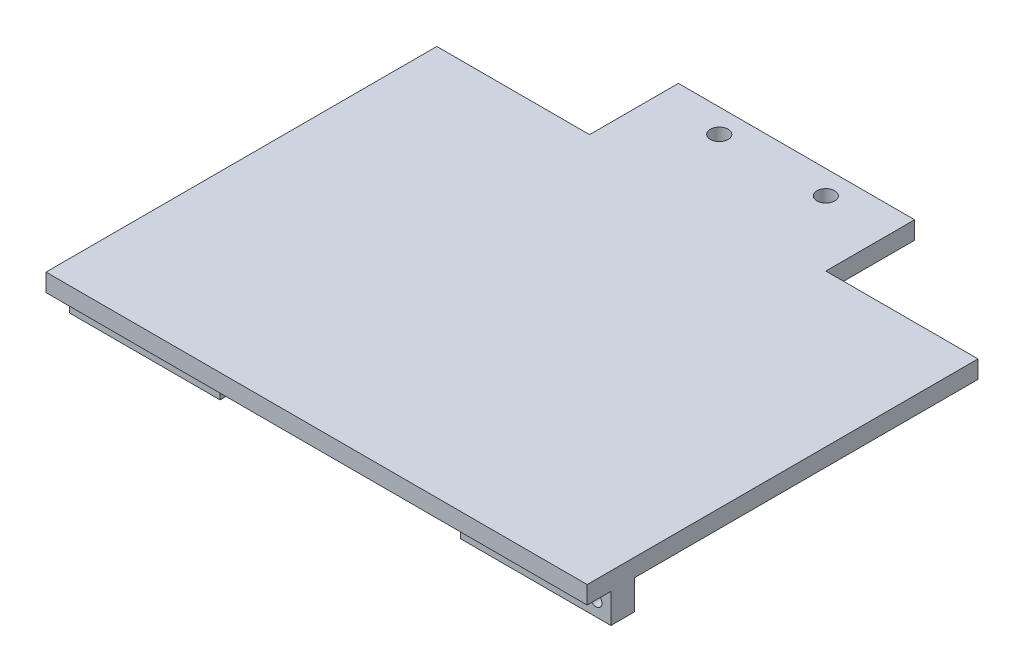
SolidWorks part; units mm, degrees
ref_plane "Front Plane" through (0, 0, 0) normal (0, 0, 1) x (1, 0, 0)
ref_plane "Top Plane" through (0, 0, 0) normal (0, 1, 0) x (1, 0, 0)
ref_plane "Right Plane" through (0, 0, 0) normal (1, 0, 0) x (0, 0, -1)
sketch "Sketch1" plane through (0, 0, 0) normal (0, 1, 0) x (1, 0, 0)
  line L1 (0, 0) -> (116.078, 0)
  line L2 (0, 0) -> (0, 102.87)
  line L3 (0, 102.87) -> (116.078, 102.87)
  line L4 (116.078, 0) -> (116.078, 102.87)
  dimension "D1" = 102.87
  dimension "D2" = 116.078
extrude "Boss-Extrude1" add sketch "Sketch1" along normal blind 3.81
sketch "Sketch2" plane through (0, 3.81, 0) normal (0, 1, 0) x (1, 0, 0)
  line L0 (116.078, 102.87) -> (0, 102.87) construction
  line L1 (0, 102.87) -> (32.766, 102.87)
  line L2 (0, 102.87) -> (0, 83.82)
  line L3 (0, 83.82) -> (32.766, 83.82)
  line L4 (32.766, 102.87) -> (32.766, 83.82)
  line L5 (116.078, 102.87) -> (83.439, 102.87)
  line L6 (116.078, 102.87) -> (116.078, 83.82)
  line L7 (116.078, 83.82) -> (83.439, 83.82)
  line L8 (83.439, 102.87) -> (83.439, 83.82)
  circle A0 centre (46.609, 97.79) radius 1.905
  circle A1 centre (69.469, 97.79) radius 1.905
  point P14 (58.039, 102.87)
  point P17 (58.039, 102.87)
  dimension "D5" = 11.43
  dimension "D8" = 3.81
  dimension "D10" = 3.81
  dimension "D1" = 19.05
  dimension "D2" = 19.05
  dimension "D3" = 32.639
  dimension "D4" = 32.766
  dimension "D6" = 11.43
  dimension "D7" = 5.08
  dimension "D9" = 5.08
extrude "Cut-Extrude1" cut sketch "Sketch2" against normal up to surface (3.81 mm away) up to face at (58.039, 0, -51.435)
sketch "Sketch3" plane through (0, 0, 0) normal (0, -1, 0) x (1, 0, 0)
  line L0 (0, -83.82) -> (0, 0) construction
  line L1 (0, -5.08) -> (32.258, -5.08)
  line L2 (0, -5.08) -> (0, -10.16)
  line L3 (0, -10.16) -> (32.258, -10.16)
  line L4 (32.258, -5.08) -> (32.258, -10.16)
  line L5 (116.078, 0) -> (116.078, -83.82) construction
  line L6 (116.078, -5.08) -> (83.82, -5.08)
  line L7 (116.078, -5.08) -> (116.078, -10.16)
  line L8 (116.078, -10.16) -> (83.82, -10.16)
  line L9 (83.82, -5.08) -> (83.82, -10.16)
  line L10 (0, 0) -> (116.078, 0) construction
  dimension "D1" = 5.08
  dimension "D2" = 5.08
  dimension "D3" = 32.258
extrude "Boss-Extrude2" add sketch "Sketch3" along normal blind 6.35
sketch "Sketch4" plane through (0, 0, -5.08) normal (0, 0, 1) x (1, 0, 0)
  line L0 (0, -6.35) -> (0, 0) construction
  line L1 (32.258, -6.35) -> (0, -6.35) construction
  line L2 (116.078, -6.35) -> (116.078, 0) construction
  circle A0 centre (3.175, -3.175) radius 1.27
  circle A1 centre (11.811, -3.175) radius 1.27
  circle A2 centre (20.447, -3.175) radius 1.27
  circle A3 centre (29.083, -3.175) radius 1.27
  circle A4 centre (86.995, -3.175) radius 1.27
  circle A5 centre (95.631, -3.175) radius 1.27
  circle A6 centre (104.267, -3.175) radius 1.27
  circle A7 centre (112.903, -3.175) radius 1.27
  dimension "D1" = 2.54
  dimension "D2" = 8.636
  dimension "D3" = 8.636
  dimension "D4" = 8.636
  dimension "D5" = 3.175
  dimension "D6" = 3.175
  dimension "D7" = 3.175
  dimension "D8" = 8.636
  dimension "D9" = 8.636
  dimension "D10" = 8.636
extrude "Cut-Extrude2" cut sketch "Sketch4" against normal up to surface (5.08 mm away) up to face at (12.0968, -3.9688, -10.16)
